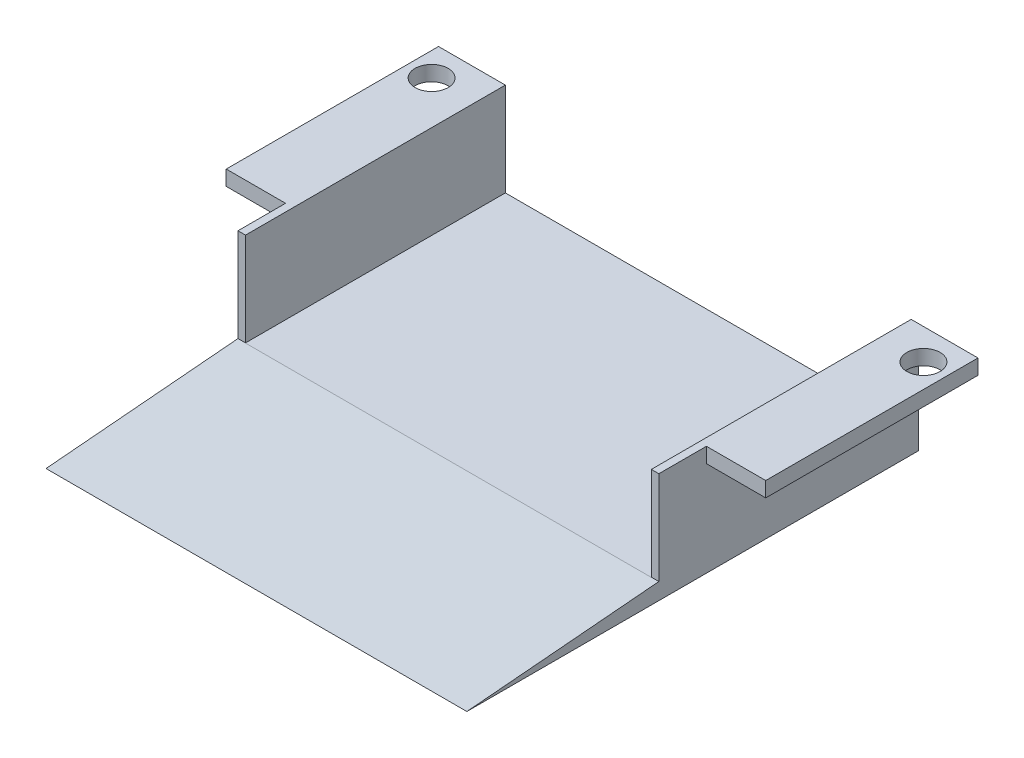
SolidWorks part; units mm, degrees
ref_plane "Front Plane" through (0, 0, 0) normal (0, 0, 1) x (1, 0, 0)
ref_plane "Top Plane" through (0, 0, 0) normal (0, 1, 0) x (1, 0, 0)
ref_plane "Right Plane" through (0, 0, 0) normal (1, 0, 0) x (0, 0, -1)
sketch "Sketch1" plane through (0, 0, 0) normal (0, 1, 0) x (1, 0, 0)
  line L1 (0, 0) -> (454.914, 0)
  line L2 (0, 0) -> (0, 381)
  line L3 (0, 381) -> (454.914, 381)
  line L4 (454.914, 0) -> (454.914, 381)
  dimension "D1" = 454.914
  dimension "D2" = 381
extrude "Boss-Extrude1" add sketch "Sketch1" along normal blind 92.6973
sketch "Sketch3" plane through (0, 92.6973, 0) normal (0, 1, 0) x (1, 0, 0)
  line L1 (454.914, 0) -> (404.9014, 0)
  line L2 (454.914, 0) -> (454.914, 202.0062)
  line L3 (454.914, 202.0062) -> (404.9014, 202.0062)
  line L4 (404.9014, 0) -> (404.9014, 202.0062)
  line L5 (0, 0) -> (50.0126, 0)
  line L6 (0, 0) -> (0, 202.0062)
  line L7 (0, 202.0062) -> (50.0126, 202.0062)
  line L8 (50.0126, 0) -> (50.0126, 202.0062)
  dimension "D1" = 202.0062
  dimension "D2" = 50.0126
  dimension "D3" = 202.0062
  dimension "D4" = 50.0126
extrude "Cut-Extrude1" cut sketch "Sketch3" against normal through all
sketch "Sketch4" plane through (0, 92.6973, 0) normal (0, 1, 0) x (1, 0, 0)
  line L0 (454.914, 381) -> (0, 381) construction
  line L1 (0, 381) -> (0, 202.0062) construction
  line L2 (454.914, 202.0062) -> (454.914, 381) construction
  circle A0 centre (20.066, 355.092) radius 14
  circle A1 centre (434.848, 355.092) radius 14
  dimension "D1" = 28
  dimension "D4" = 28
  dimension "D5" = 20.066
  dimension "D6" = 25.908
  dimension "D2" = 25.908
  dimension "D3" = 20.066
extrude "Cut-Extrude2" cut sketch "Sketch4" against normal through all
sketch "Sketch5" plane through (0, 92.6973, 0) normal (0, 1, 0) x (1, 0, 0)
  line L0 (454.914, 381) -> (0, 381) construction
  line L1 (56.3626, 381) -> (398.5514, 381)
  line L2 (56.3626, 381) -> (56.3626, 0)
  line L3 (56.3626, 0) -> (398.5514, 0)
  line L4 (398.5514, 381) -> (398.5514, 0)
  line L5 (50.0126, 0) -> (404.9014, 0) construction
  line L6 (50.0126, 0) -> (50.0126, 202.0062) construction
  line L7 (404.9014, 202.0062) -> (404.9014, 0) construction
  dimension "D1" = 6.35
  dimension "D2" = 6.35
extrude "Cut-Extrude3" cut sketch "Sketch5" against normal blind 78.74
sketch "Sketch6" plane through (454.914, 0, 0) normal (1, 0, 0) x (0, 0, -1)
  line L0 (381, 92.6973) -> (381, 0) construction
  line L1 (202.0062, 0) -> (381, 0)
  line L2 (202.0062, 0) -> (202.0062, 79.9974)
  line L3 (202.0062, 79.9974) -> (381, 79.9974)
  line L4 (381, 0) -> (381, 79.9974)
  dimension "D1" = 79.9974
extrude "Cut-Extrude4" cut sketch "Sketch6" against normal blind 50.0126
sketch "Sketch7" plane through (0, 0, 0) normal (-1, 0, 0) x (0, 0, 1)
  line L0 (-202.0062, 0) -> (-202.0062, 92.6973) construction
  line L1 (-381, 0) -> (-202.0062, 0)
  line L2 (-381, 0) -> (-381, 79.9974)
  line L3 (-381, 79.9974) -> (-202.0062, 79.9974)
  line L4 (-202.0062, 0) -> (-202.0062, 79.9974)
  dimension "D1" = 79.9974
extrude "Cut-Extrude5" cut sketch "Sketch7" against normal blind 50.0126
sketch "Sketch10" plane through (404.9014, 0, 0) normal (1, 0, 0) x (0, 0, -1)
  line L0 (0, 0) -> (161.8995, 13.97)
  line L1 (202.0062, 92.6973) -> (0, 92.6973) construction
  line L3 (161.8995, 92.6973) -> (161.8995, 13.97)
  line L8 (161.8995, 92.6973) -> (0, 92.6973)
  line L9 (0, 92.6973) -> (0, 0)
extrude "Cut-Extrude6" cut sketch "Sketch10" against normal through all
